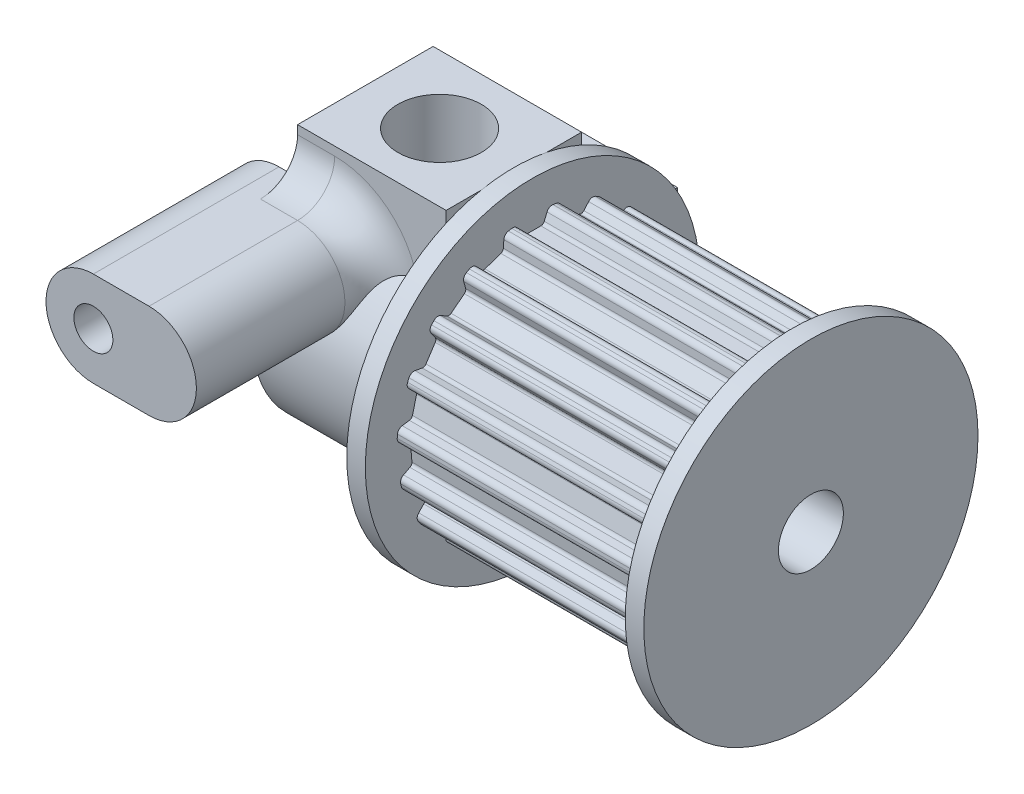
SolidWorks part; units mm, degrees
material "PLA Black"
ref_plane "Front" through (0, 0, 0) normal (0, 0, 1) x (1, 0, 0)
ref_plane "Top" through (0, 0, 0) normal (0, 1, 0) x (1, 0, 0)
ref_plane "Right" through (0, 0, 0) normal (1, 0, 0) x (0, 0, -1)
sketch "Sketch1" plane through (0, 0, 0) normal (1, 0, 0) x (0, 0, -1)
  line L0 (1.118, 1) -> (-1.118, 1) construction
  line L1 (-3.65, 4.8249) -> (3.65, 4.8249)
  line L2 (4.8249, 3.65) -> (4.8249, -3.65)
  line L3 (0, 0) -> (11.6334, 0) construction
  line L4 (0, 0) -> (0, 8.6732) construction
  arc A0 (-1.118, 1) -> (1.118, 1) centre (0, 0) ccw construction
  circle A1 centre (0, 0) radius 1.75
  arc A2 (4.8249, -3.65) -> (-3.65, 4.8249) centre (0, 0) cw
  arc A3 (4.8249, 3.65) -> (3.65, 4.8249) centre (0, 0) ccw
  dimension "D1" = 3
  dimension "D3" = 0.25
  dimension "D5" = 6.05
  dimension "D2" = 1
  dimension "D4" = 7.3
extrude "Boss-Extrude1" add sketch "Sketch1" along normal mid plane 8
sketch "Sketch2" plane through (0, 4.8249, 0) normal (0, 1, 0) x (1, 0, 0)
  circle A0 centre (0, 0) radius 2.25
  dimension "D1" = 4.5
extrude "Cut-Extrude1" cut sketch "Sketch2" against normal blind 5
sketch "Sketch7" plane through (4, 0, 0) normal (1, 0, 0) x (0, 0, -1)
  circle A0 centre (0, 0) radius 1.75 construction
  circle A1 centre (0, 0) radius 7.3
  circle A2 centre (0, 0) radius 1.75
  dimension "D1" = 14.6
extrude "Boss-Extrude5" add sketch "Sketch7" along normal blind 15
sketch "Sketch8" plane through (19, 0, 0) normal (1, 0, 0) x (0, 0, -1)
  line L0 (-0.4541, 6.5499) -> (0.4528, 6.5499)
  line L1 (0.6374, 6.6734) -> (0.7865, 7.0333)
  line L2 (-0.6389, 6.6734) -> (-0.788, 7.0333)
  line L6 (0, 9.2013) -> (0, 0) construction
  arc A0 (0.4528, 6.5499) -> (0.6374, 6.6734) centre (0.4526, 6.7499) ccw
  arc A1 (-0.4541, 6.5499) -> (-0.6389, 6.6734) centre (-0.4541, 6.7499) cw
  arc A2 (0.7865, 7.0333) -> (1.1093, 7.2152) centre (1.0638, 6.9187) cw
  arc A3 (-0.788, 7.0333) -> (-1.1108, 7.215) centre (-1.0652, 6.9185) ccw
  circle A4 centre (0, 0) radius 7.3 construction
  arc A5 (-1.1108, 7.215) -> (1.1093, 7.2152) centre (0, 0) cw
  point P3 (-0.0007, 6.5499)
  point P15 (0, 9.84)
extrude "Cut-Extrude3" cut sketch "Sketch8" against normal up to surface (15 mm away) up to face at (4, 0, -7.3)
pattern_circular "CirPattern1" count 19 over 360 about axis through (19, 0, 0) along (-1, 0, 0) of "Cut-Extrude3"
sketch "Sketch9" plane through (19, 0, 0) normal (1, 0, 0) x (0, 0, -1)
  circle A0 centre (0, 0) radius 9
  circle A1 centre (0, 0) radius 1.75 construction
  circle A2 centre (0, 0) radius 1.75
  dimension "D1" = 18
extrude "Boss-Extrude6" add sketch "Sketch9" along normal blind 1
sketch "Sketch10" plane through (4, 0, 0) normal (-1, 0, 0) x (0, 0, 1)
  circle A0 centre (0, 0) radius 9
  circle A1 centre (0, 0) radius 9 construction
  circle A2 centre (0, 0) radius 1.75 construction
  circle A3 centre (0, 0) radius 1.75
extrude "Boss-Extrude7" add sketch "Sketch10" against normal blind 1
sketch "Sketch3" plane through (0, 0, -4.8249) normal (0, 0, -1) x (-1, 0, 0)
  circle A0 centre (0, 0) radius 2.25
  dimension "D1" = 4.5
extrude "Cut-Extrude2" cut sketch "Sketch3" against normal blind 5
sketch "Sketch4" plane through (0, 4.8249, 0) normal (0, 1, 0) x (1, 0, 0)
  line L0 (4, 3.65) -> (-4, 3.65) construction
  line L2 (4, -3.65) -> (-4, -3.65) construction
  line L3 (-4, 3.65) -> (-4, -3.65) construction
  line L4 (4, 3.65) -> (-4, 3.65)
  line L5 (4, 3.65) -> (4, -3.65)
  line L6 (4, -3.65) -> (-4, -3.65)
  line L7 (-4, 3.65) -> (-4, -3.65)
  line L8 (4, 7.3) -> (4, -7.3) construction
  circle A0 centre (0, 0) radius 2.25 construction
  circle A1 centre (0, 0) radius 2.25
extrude "Boss-Extrude2" add sketch "Sketch4" along normal blind 4
sketch "Sketch5" plane through (0, 0, -4.8249) normal (0, 0, -1) x (-1, 0, 0)
  line L0 (-4, 3.65) -> (4, 3.65) construction
  line L1 (4, -3.65) -> (4, 3.65) construction
  line L2 (-4, -3.65) -> (4, -3.65) construction
  line L4 (-4, 3.65) -> (4, 3.65)
  line L5 (4, -3.65) -> (4, 3.65)
  line L6 (-4, -3.65) -> (4, -3.65)
  line L7 (-4, -3.65) -> (-4, 3.65)
  line L8 (-4, -7.3) -> (-4, 7.3) construction
  circle A0 centre (0, 0) radius 2.25 construction
  circle A1 centre (0, 0) radius 2.25
extrude "Boss-Extrude3" add sketch "Sketch5" along normal blind 4
ref_axis "Axis1" through (20, 0, 0) along (-1, 0, 0)
sketch "Sketch6" plane through (0, 0, 3.65) normal (0, 0, 1) x (1, 0, 0)
  line L0 (-4, 8.8249) -> (-4, 4.8249) construction
  line L2 (-2, 6.3555) -> (-5, 6.3555)
  line L3 (-5, 1.2545) -> (-2, 1.2545)
  line L6 (20, 0) -> (-4, 0) construction
  circle A0 centre (-5, 3.805) radius 1.0505
  arc A1 (-5, 6.3555) -> (-5, 1.2545) centre (-5, 3.805) ccw
  arc A2 (-2, 6.3555) -> (-2, 1.2545) centre (-2, 3.805) cw
  dimension "D1" = 2.101
  dimension "D2" = 3.805
  dimension "D3" = 1.5
  dimension "D4" = 1
  dimension "D5" = 3
extrude "Boss-Extrude4" add sketch "Sketch6" along normal blind 10
fillet "Fillet1" radius 2 2 edges at (-0.6029, 5.9388, 3.65) (-3, 6.3555, 3.65)
equation "\"knee_angle\"= 0"
equation "\"ankle_angle\" = 90"
equation "\"hip_angle\" = 0"
equation "\"spring_ankle_parallel_arm_diameter\"= 1.5"
equation "\"spring_ankle_parallel_arm_length\"= 13"
equation "\"spring_ankle_parallel_intern_diameter\"= 5.7"
equation "\"spring_ankle_parallel_angle\"= \"ankle_angle\""
equation "\"spring_ankle_parallel_turns\"= 3"
equation "\"spring_ankle_parallel_pitch\"= \"spring_ankle_parallel_arm_diameter\" * 1.01"
equation "\"spring_ankle_parallel_cutting_distance\"= (1-\"spring_ankle_parallel_angle\" / 360) * \"spring_ankle_parallel_pitch\""
equation "\"spring_ankle_serial_arm_diameter\"= 1.91"
equation "\"spring_ankle_serial_arm_length\"= 10"
equation "\"spring_ankle_serial_intern_diameter\"= 5.7"
equation "\"spring_ankle_serial_angle\"= \"90\""
equation "\"spring_ankle_serial_turns\"= 3"
equation "\"spring_ankle_serial_pitch\"= \"spring_ankle_serial_arm_diameter\" * 1.01"
equation "\"spring_ankle_serial_cutting_distance\"= (1-\"spring_ankle_serial_angle\" / 360) * \"spring_ankle_serial_pitch\""
equation "\"spring_knee_parallel_arm_diameter\"= 1.5"
equation "\"spring_knee_parallel_arm_length\"= 13"
equation "\"spring_knee_parallel_intern_diameter\"= 5.7"
equation "\"spring_knee_parallel_angle\"= -\"knee_angle\" + 90"
equation "\"spring_knee_parallel_turns\"= 3"
equation "\"spring_knee_parallel_pitch\"= \"spring_knee_parallel_arm_diameter\" * 1.01"
equation "\"spring_knee_parallel_cutting_distance\"= (1-(\"spring_knee_parallel_angle\") / 360) * \"spring_knee_parallel_pitch\""
equation "\"spring_knee_serial_arm_diameter\"= 1.91"
equation "\"spring_knee_serial_arm_length\"= 10"
equation "\"spring_knee_serial_intern_diameter\"= 5.7"
equation "\"spring_knee_serial_angle\"= \"90\""
equation "\"spring_knee_serial_turns\"= 3"
equation "\"spring_knee_serial_pitch\"= \"spring_knee_serial_arm_diameter\" * 1.01"
equation "\"spring_knee_serial_cutting_distance\"= (1-\"spring_knee_serial_angle\" / 360) * \"spring_knee_serial_pitch\""
equation "\"D2@Sketch6\" = ( \"spring_ankle_serial_intern_diameter\" + \"spring_ankle_serial_arm_diameter\" ) / 2"
equation "\"D1@Sketch6\" = \"spring_ankle_serial_arm_diameter\" * 1.1"
